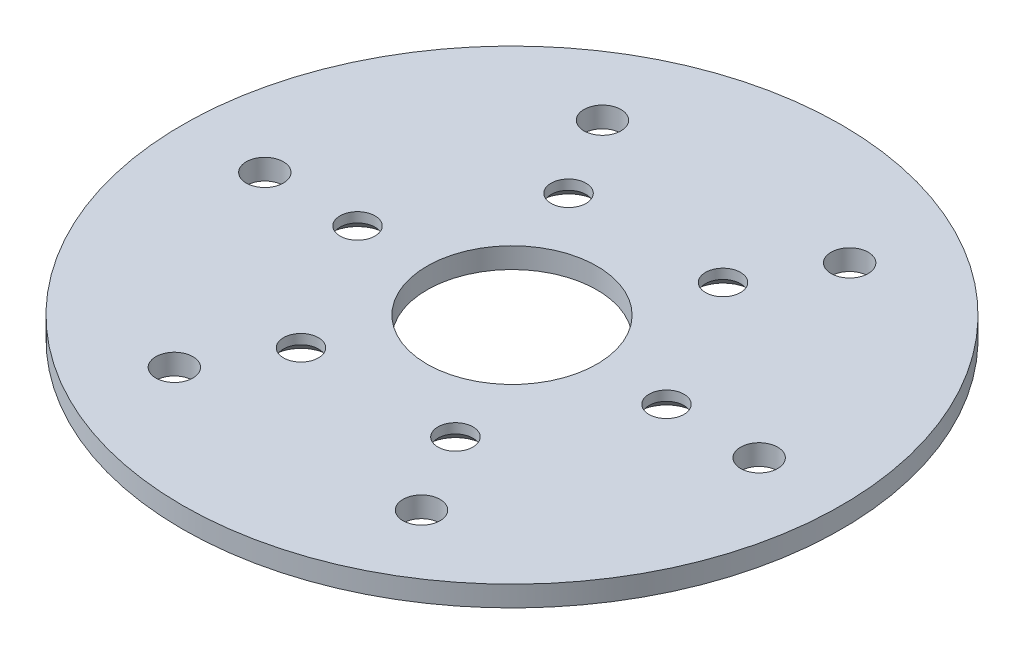
SolidWorks part; units mm, degrees
ref_plane "Front Plane" through (0, 0, 0) normal (0, 0, 1) x (1, 0, 0)
ref_plane "Top Plane" through (0, 0, 0) normal (0, 1, 0) x (1, 0, 0)
ref_plane "Right Plane" through (0, 0, 0) normal (1, 0, 0) x (0, 0, -1)
sketch "Sketch1" plane through (0, 0, 0) normal (0, 1, 0) x (1, 0, 0)
  circle A0 centre (0, 0) radius 8.25
  circle A1 centre (0, 0) radius 32
  dimension "D1" = 16.5
  dimension "D2" = 64
extrude "Boss-Extrude1" add sketch "Sketch1" along normal blind 2
sketch "Sketch2" plane through (0, 2, 0) normal (0, 1, 0) x (1, 0, 0)
  circle A0 centre (0, 21) radius 4
  circle A1 centre (0, 0) radius 21 construction
  circle A2 centre (18.1865, 10.5) radius 4
  circle A3 centre (18.1865, -10.5) radius 4
  circle A4 centre (0, -21) radius 4
  circle A5 centre (-18.1865, -10.5) radius 4
  circle A6 centre (-18.1865, 10.5) radius 4
  point P17 (0, 0)
  dimension "D1" = 8
  dimension "D2" = 42
  dimension "D3" = 6
extrude "Cut-Extrude1" [suppressed] cut sketch "Sketch2" against normal through all and the other way through all
hole_wizard "CSK for M3 Hex Socket Countersunk Head Screw1" positions "Sketch3" profile "Sketch4" countersink size "M3" standard "DIN" end condition up to next
sketch "Sketch3" plane through (0, 0, 0) normal (0, 1, 0) x (1, 0, 0)
  line L0 (0, 0) -> (18.891, 32.7202) construction
  circle A0 centre (0, 0) radius 15
  point P8 (7.5, 12.9904)
  point P14 (15, 0)
  point P15 (7.5, -12.9904)
  point P16 (-7.5, -12.9904)
  point P17 (-15, 0)
  point P18 (-7.5, 12.9904)
  dimension "D2" = 30
  dimension "D1" = 60
  dimension "D3" = 6
sketch "Sketch4" plane through (-7.5, 0, -12.9904) normal (1, 0, 0) x (0, 0, -1)
  line L0 (0, 0) -> (0, 2)
  line L1 (0, 2) -> (1.7, 2)
  line L2 (1.7, 2) -> (1.7, 1.05)
  line L3 (1.7, 1.05) -> (2.75, 0)
  line L5 (2.75, 0) -> (0, 0)
  line L6 (-1.7, 1.05) -> (-2.75, 0) construction
  line L11 (0, -6.35) -> (0, 107.95) construction
  dimension "Thru Hole Dia." = 3.4
  dimension "Thru Hole Depth" = 2
  dimension "Near C'Sink Dia." = 5.5
  dimension "Near C'Sink Angle" = 90
hole_wizard "M3 Clearance Hole1" positions "Sketch5" profile "Sketch7" hole size "M3" standard "DIN" end condition up to next
sketch "Sketch5" plane through (0, 0, 0) normal (0, -1, 0) x (-1, 0, 0)
  circle A0 centre (0, 0) radius 24
  point P6 (-24, 0)
  point P14 (-12, 20.7846)
  point P15 (12, 20.7846)
  point P16 (24, 0)
  point P17 (12, -20.7846)
  point P18 (-12, -20.7846)
  dimension "D1" = 48
sketch "Sketch7" plane through (12, 0, 20.7846) normal (1, 0, 0) x (0, 0, -1)
  line L0 (0, 0) -> (0, 2)
  line L1 (0, 2) -> (1.8, 2)
  line L2 (1.8, 2) -> (1.8, 0)
  line L5 (1.8, 0) -> (0, 0)
  line L11 (0, -6.35) -> (0, 107.95) construction
  dimension "Thru Hole Dia." = 3.6
  dimension "Thru Hole Depth" = 2
